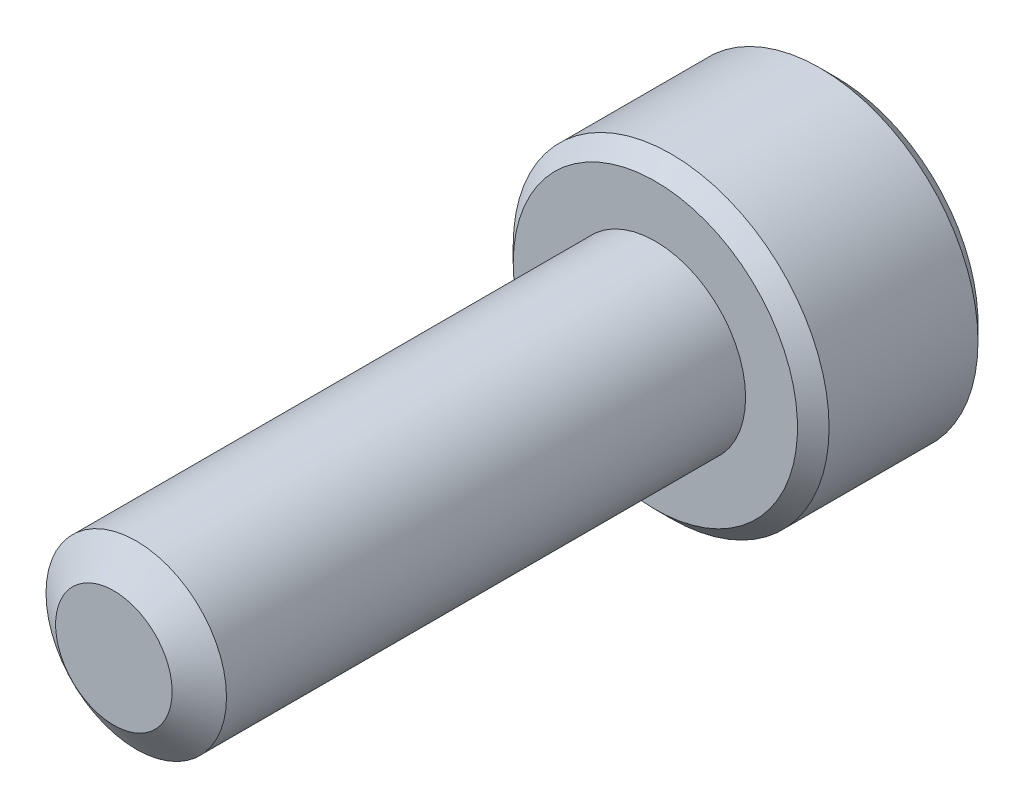
SolidWorks part; units mm, degrees
other "DetailItem1"
material "1.4310 (X10CrNi18-8)"
ref_plane "Front Plane" through (0, 0, 0) normal (0, 0, 1) x (1, 0, 0)
ref_plane "Top Plane" through (0, 0, 0) normal (0, 1, 0) x (1, 0, 0)
ref_plane "Right Plane" through (0, 0, 0) normal (1, 0, 0) x (0, 0, -1)
sketch "Sketch1" plane through (0, 0, 0) normal (0, 0, 1) x (1, 0, 0)
  circle A0 centre (0, 0) radius 2
  dimension "OD" = 4
extrude "Extrude1" add sketch "Sketch1" against normal blind 12
sketch "Sketch2" plane through (0, 0, 0) normal (0, 0, 1) x (1, 0, 0)
  circle A0 centre (0, 0) radius 2 construction
  circle A1 centre (0, 0) radius 2
curve "Helix/Spiral1" pitch 0.7 height 12.7 turns 18.1429 parameters "pitch"=0.7
sketch "Sketch3" plane through (0, 0, 0) normal (1, 0, 0) x (0, 0, -1)
  line L0 (-0.6125, 2) -> (-0.35, 1.5453)
  line L1 (-0.35, 1.5453) -> (-0.2625, 1.5453)
  line L2 (-0.2625, 1.5453) -> (0, 2)
  line L3 (-0.6125, 2) -> (0, 2)
  line L4 (-0.3062, 2) -> (-0.3062, 1.5453) construction
  line L5 (-0.4812, 1.7727) -> (-0.1312, 1.7727) construction
  line L6 (0, 2) -> (0, -2) construction
  dimension "D1" = 0.0875
  dimension "D2" = 0.35
  dimension "D3" = 60
sweep "Cut-Sweep1" [suppressed] cut profiles "Sketch3" path "Helix/Spiral1"
sketch "Sketch4" plane through (0, 0, 0) normal (1, 0, 0) x (0, 0, -1)
  line L0 (0.4962, 2) -> (0, 1.2913)
  line L1 (0, 1.2913) -> (0, 2)
  line L2 (0.4962, 2) -> (0, 2)
  line L3 (-0.6125, 2) -> (0, 2) construction
  line L4 (0, 0) -> (7.0209, 0) construction
  dimension "D1" = 55
  dimension "D2" = 0.254
revolve "Cut-Revolve1" cut sketch "Sketch4" angle 360 about L4
sketch "Sketch6" plane through (0, 0, -12) normal (0, 0, -1) x (-1, 0, 0)
  circle A0 centre (0, 0) radius 3.5
  dimension "head dia" = 7
extrude "Extrude2" add sketch "Sketch6" along normal blind 4
sketch "Sketch7" plane through (0, 0, -16) normal (0, 0, -1) x (-1, 0, 0)
  line L1 (0, 1.7321) -> (-1.5, 0.866)
  line L2 (-1.5, 0.866) -> (-1.5, -0.866)
  line L3 (-1.5, -0.866) -> (0, -1.7321)
  line L4 (0, -1.7321) -> (1.5, -0.866)
  line L5 (1.5, -0.866) -> (1.5, 0.866)
  line L6 (1.5, 0.866) -> (0, 1.7321)
  circle A0 centre (0, 0) radius 1.5 construction
  dimension "hex dia" = 3
extrude "Cut-Extrude1" cut sketch "Sketch7" against normal blind 2.25
sketch "Sketch8" plane through (0, 0, -16) normal (0, 0, -1) x (-1, 0, 0)
  circle A0 centre (0, 0) radius 1.7321
extrude "Cut-Extrude2" cut sketch "Sketch8" against normal through all draft 45
chamfer "Chamfer1" distance 0.35 angle 45 2 edges at (-3.5, 0, -16) (-3.5, 0, -12)
sketch "Sketch10" plane through (0, 0, -12) normal (0, 0, 1) x (1, 0, 0)
  circle A1 centre (0, 0) radius 2
  circle A2 centre (0, 0) radius 2
  dimension "D1" = 0
ref_plane "Plane1" through (0, 0, 0) normal (0, 0, 1) x (1, 0, 0)
extrude "partial thread" [suppressed] add sketch "Sketch10" along normal up to surface (10 mm away) separate body up to plane "Plane1"
chamfer "Chamfer2" [suppressed] distance 0.08 angle 45
combine bodies "Combine1" [suppressed] operation type add bodies to combine 107 108
sketch "Sketch9" plane through (0, 0, 0) normal (1, 0, 0) x (0, 0, -1)
  line L0 (0, 2) -> (0, -2) construction
  line L1 (1.75, 2) -> (1.75, -2) construction
  dimension "D1" = 1.75
equation "\"D3@Helix/Spiral1\" = \"screw length@Extrude1\"+\"pitch@Helix/Spiral1\""
equation "\"D1@Sketch3\" = \"pitch@Helix/Spiral1\"*.125"
equation "\"D2@Sketch3\" = \"pitch@Helix/Spiral1\"*.5"
equation "\"D1@Cut-Extrude1\" = \"hex dia@Sketch7\"*.75"
equation "\"D1@Chamfer1\" = \"head dia@Sketch6\"*.05"
equation "\"D1@Sketch9\" = \"pitch@Helix/Spiral1\"*2.5"
equation "\"D1@Chamfer2\"=\"OD@Sketch1\"*.02"
